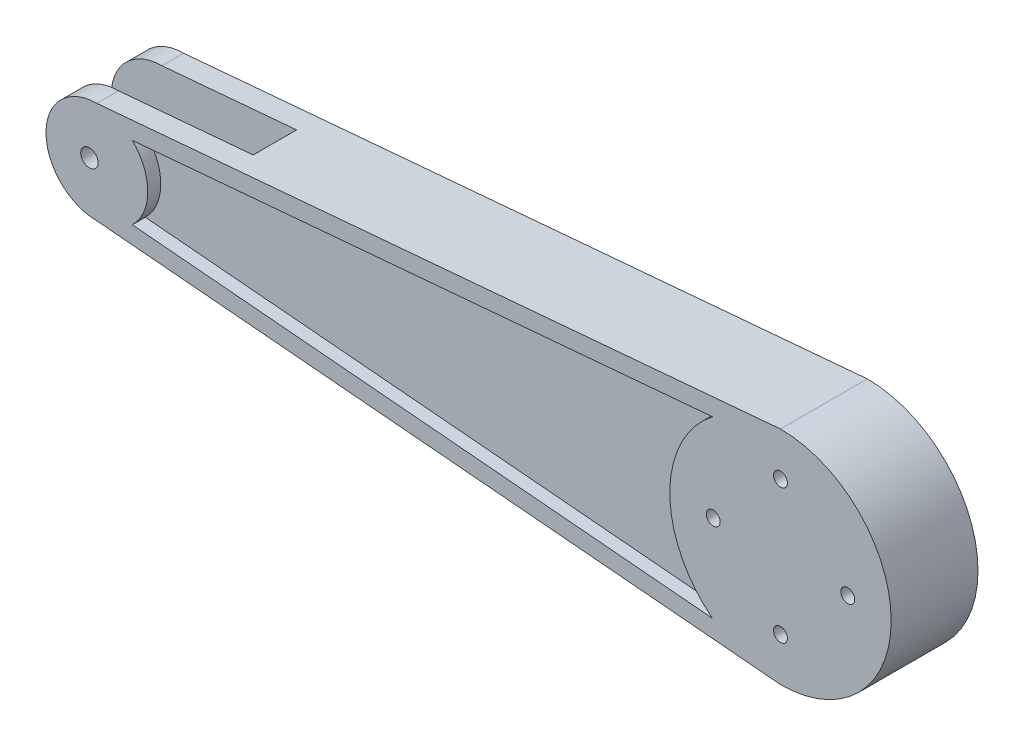
SolidWorks part; units mm, degrees
ref_plane "Front Plane" through (0, 0, 0) normal (1, 0, 0) x (0, 1, 0)
ref_plane "Top Plane" through (0, 0, 0) normal (0, 0, 1) x (0, 1, 0)
ref_plane "Right Plane" through (0, 0, 0) normal (0, 1, 0) x (-1, 0, 0)
sketch "Sketch1" plane through (0, 0, 0) normal (0, 0, 1) x (-1, 0, 0)
  line L17 (194.7068, 0) -> (186.7068, 0)
  line L21 (161.7175, 0) -> (182.7068, 0)
  line L24 (0, 0) -> (8.4, 0)
  line L25 (25.5, 25.5) -> (182.985, 11.7218)
  line L26 (11.6, 0) -> (39.4, 0)
  line L27 (42.6, 0) -> (161.7175, 0)
  arc A9 (182.985, 11.7218) -> (194.7068, 0) centre (182.985, 0) cw
  circle A13 centre (182.985, 0) radius 11.7218 construction
  arc A14 (25.5, 25.5) -> (0, 0) centre (25.5, 0) ccw
  circle A15 centre (25.5, 0) radius 15.5 construction
  arc A16 (11.6, 0) -> (8.4, 0) centre (10, 0) ccw
  circle A17 centre (25.5, 15.5) radius 1.6
  arc A18 (42.6, 0) -> (39.4, 0) centre (41, 0) ccw
  circle A19 centre (25.5, -15.5) radius 1.6 construction
  arc A20 (186.7068, 0) -> (182.7068, 0) centre (184.7068, 0) ccw
  dimension "D4" = 31
  dimension "D12" = 3.2
  dimension "D5" = 4
  dimension "D7" = 10
  dimension "D8" = 22.9893
  dimension "D3" = 157.485
  dimension "D10" = 10
  dimension "D11" = 3.2
  dimension "D13" = 4
  dimension "D6" = 5
  dimension "D2" = 4
extrude "Boss-Extrude1" add sketch "Sketch1" along normal blind 20
mirror "Mirror1" about plane through (0, 0, 20) normal (0, -1, 0) of "Boss-Extrude1"
ref_plane "Plane1" through (0, 0, 10) normal (0, 0, 1) x (1, 0, 0)
sketch "Sketch2" plane through (0, 0, 10) normal (0, 0, 1) x (1, 0, 0)
  line L0 (-174.6964, -8.2886) -> (-151.9727, 14.4351) construction
  line L1 (-182.985, 11.7218) -> (-25.5, 25.5) construction
  line L2 (-182.985, -11.7218) -> (-25.5, -25.5) construction
  line L3 (-151.9727, 14.4351) -> (-182.985, 11.7218)
  line L4 (-182.985, -11.7218) -> (-151.9727, -14.4351)
  line L10 (-151.9727, 14.4351) -> (-151.9727, -14.4351)
  arc A0 (-182.985, 11.7218) -> (-182.985, -11.7218) centre (-182.985, 0) ccw
  arc A4 (-182.985, 11.7218) -> (-182.985, -11.7218) centre (-182.985, 0) cw construction
  arc A8 (-182.985, 11.7218) -> (-182.985, -11.7218) centre (-182.985, 0) ccw construction
  dimension "D1" = 45
extrude "Cut-Extrude1" cut sketch "Sketch2" against normal blind 5 and the other way blind 5 contours L3 A0 L4 L10 region at (-171.3595, 0, 10)
sketch "Sketch3" plane through (0, 0, 20) normal (0, 0, 1) x (1, 0, 0)
  line L0 (-174.83, 8.42) -> (-41.1749, 20.1133)
  line L1 (-174.83, -8.42) -> (-41.1749, -20.1133)
  line L2 (-182.985, 11.7218) -> (-25.5, 25.5) construction
  line L3 (-182.985, -11.7218) -> (-25.5, -25.5) construction
  arc A0 (-174.83, -8.42) -> (-174.83, 8.42) centre (-182.985, 0) ccw
  arc A1 (-41.1749, 20.1133) -> (-41.1749, -20.1133) centre (-25.5, 0) ccw
  arc A2 (-25.5, -25.5) -> (-25.5, 25.5) centre (-25.5, 0) ccw construction
  arc A3 (-182.985, 11.7218) -> (-182.985, -11.7218) centre (-182.985, 0) ccw construction
  dimension "D1" = 4
  dimension "D2" = 4
extrude "Cut-Extrude2" cut sketch "Sketch3" against normal blind 3 contours L0 A1 L1 A0
mirror "Mirror2" about plane through (0, 0, 10) normal (0, 0, 1) of "Cut-Extrude2"
equation "\"ThighLength\"= 200"
equation "\"BearingBore\"=4"
equation "\"MinShinWidth\"= 20"
equation "\"HipBore\"=27"
equation "\"ShinThickness\"=10"
equation "\"ThighThickness\"=20"
equation "\"D1@Boss-Extrude1\"=\"ThighThickness\""
equation "\"D2@Cut-Extrude1\"=\"ShinThickness\"/2"
equation "\"D1@Cut-Extrude1\"=\"ShinThickness\"/2"
equation "\"MaxBending\"=135"
equation "\"D1@Sketch2\"=180-\"MaxBending\""
equation "\"MaxStretchingAngle\"= 140"
equation "\"KneeLength\" =20"
equation "\"ThighJointDistance\"=157.485"
equation "\"D3@Sketch1\"=\"ThighJointDistance\""
